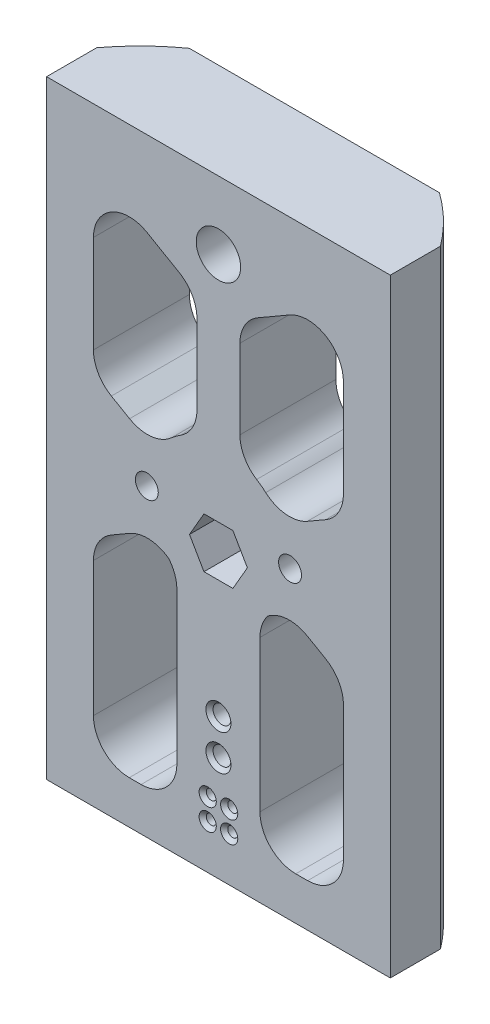
SolidWorks part; units mm, degrees
ref_plane "Front Plane" through (0, 0, 0) normal (0, 0, 1) x (1, 0, 0)
ref_plane "Top Plane" through (0, 0, 0) normal (0, 1, 0) x (1, 0, 0)
ref_plane "Right Plane" through (0, 0, 0) normal (1, 0, 0) x (0, 0, -1)
sketch "Sketch1" plane through (0, 0, 0) normal (0, 0, 1) x (1, 0, 0)
  line L0 (-2.275, -128.15) -> (-2.275, -128.6)
  line L1 (2.275, -128.15) -> (2.275, -128.6)
  line L2 (-2.275, -133.15) -> (-2.275, -134.025)
  line L3 (2.275, -133.15) -> (2.275, -134.025)
  line L11 (-2.275, -128.15) -> (2.275, -128.15)
  line L12 (2.275, -128.15) -> (2.275, -123.6)
  line L13 (2.275, -123.6) -> (-2.275, -123.6)
  line L14 (-2.275, -123.6) -> (-2.275, -128.15)
  line L15 (-2.275, -128.15) -> (2.275, -128.15)
  line L16 (2.275, -128.15) -> (2.275, -123.6)
  line L17 (2.275, -123.6) -> (-2.275, -123.6)
  line L18 (-2.275, -123.6) -> (-2.275, -128.15)
  line L24 (-2.275, -133.15) -> (2.275, -133.15)
  line L25 (2.275, -133.15) -> (2.275, -128.6)
  line L26 (2.275, -128.6) -> (-2.275, -128.6)
  line L27 (-2.275, -128.6) -> (-2.275, -133.15)
  line L28 (-2.275, -133.15) -> (2.275, -133.15)
  line L29 (2.275, -133.15) -> (2.275, -128.6)
  line L30 (2.275, -128.6) -> (-2.275, -128.6)
  line L31 (-2.275, -128.6) -> (-2.275, -133.15)
  line L37 (0, -123.6) -> (0, -142.4) construction
  line L39 (7, -120.5) -> (-7, -120.5)
  line L40 (7, -120.5) -> (7, -145.5)
  line L41 (7, -145.5) -> (-7, -145.5)
  line L42 (-7, -120.5) -> (-7, -145.5)
  line L43 (7, -120.5) -> (-7, -145.5) construction
  line L44 (7, -145.5) -> (-7, -120.5) construction
  line L45 (-1, -142.4) -> (1, -142.4)
  line L46 (1, -142.4) -> (1, -141.625)
  line L47 (1, -141.625) -> (3.8, -141.625)
  line L48 (3.8, -141.625) -> (3.8, -134.025)
  line L49 (3.8, -134.025) -> (-3.8, -134.025)
  line L50 (-3.8, -134.025) -> (-3.8, -141.625)
  line L51 (-3.8, -141.625) -> (-1, -141.625)
  line L52 (-1, -141.625) -> (-1, -142.4)
  line L53 (-1, -142.4) -> (1, -142.4)
  line L54 (1, -142.4) -> (1, -141.625)
  line L55 (1, -141.625) -> (3.8, -141.625)
  line L56 (3.8, -141.625) -> (3.8, -134.025)
  line L57 (3.8, -134.025) -> (-3.8, -134.025)
  line L58 (-3.8, -134.025) -> (-3.8, -141.625)
  line L59 (-3.8, -141.625) -> (-1, -141.625)
  line L60 (-1, -141.625) -> (-1, -142.4)
  circle A0 centre (0, -125.875) radius 1.275
  circle A1 centre (0, -130.875) radius 1.275
  circle A2 centre (-1.5, -139.325) radius 0.65
  circle A3 centre (-1.5, -136.325) radius 0.65
  circle A4 centre (1.5, -136.325) radius 0.65
  circle A5 centre (1.5, -139.325) radius 0.65
  point P25 (0, -133)
  dimension "D4" = 2.55
  dimension "D5" = 1.3
  dimension "D6" = 25
  dimension "D7" = 14
  dimension "D1" = 0.2
  dimension "D2" = 0.2
  dimension "D3" = 0.2
extrude "Boss-Extrude1" add sketch "Sketch1" against normal blind 6.4 contours L39 L42 L41 L40 L60 L59 L58 L57 L31 L18 L17 L16 L29 L56 L55 L54 L53 region at (6.7135, -133, 0)
sketch "Sketch3" plane through (0, 0, 0) normal (0, 0, 1) x (1, 0, 0)
  line L4 (7, -120.5) -> (-7, -120.5)
  line L5 (-7, -120.5) -> (-7, -145.5)
  line L6 (-7, -145.5) -> (7, -145.5)
  line L7 (7, -145.5) -> (7, -120.5)
  line L8 (7, -120.5) -> (-7, -120.5)
  line L9 (-7, -120.5) -> (-7, -145.5)
  line L10 (-7, -145.5) -> (7, -145.5)
  line L11 (7, -145.5) -> (7, -120.5)
  circle A0 centre (-1.5, -139.325) radius 0.7
  circle A1 centre (-1.5, -136.325) radius 0.7
  circle A2 centre (1.5, -136.325) radius 0.7
  circle A3 centre (1.5, -139.325) radius 0.7
  circle A4 centre (0, -130.875) radius 1.25
  circle A5 centre (0, -125.875) radius 1.25
  dimension "D2" = 2.5
  dimension "D3" = 1.4
  dimension "D1" = 0
extrude "Boss-Extrude3" add sketch "Sketch3" along normal blind 7
chamfer "Chamfer1" distance 0.5 angle 45 6 edges at (2.2, -139.325, 7) (-0.8, -139.325, 7) (-0.8, -136.325, 7) (2.2, -136.325, 7) (1.25, -130.875, 7) (1.25, -125.875, 7)
sketch "Sketch4" plane through (0, -145.5, 0) normal (0, -1, 0) x (1, 0, 0)
  line L0 (-7, -6.4) -> (-17.4539, -6.4)
  line L1 (-7, 7) -> (-27.9106, 7)
  line L2 (7, -6.4) -> (17.4539, -6.4)
  line L3 (7, 7) -> (27.9106, 7)
  line L4 (-24, 0) -> (-24, 7)
  line L5 (24, 0) -> (24, 7)
  circle A4 centre (0, 18) radius 30
  arc A5 (-24, 0) -> (24, 0) centre (0, 18) ccw construction
  line M2 (7, -6.4) -> (7, 7)
  line M4 (-7, 7) -> (-7, -6.4)
extrude "Boss-Extrude4" add sketch "Sketch4" against normal up to surface (25 mm away) contours L1 A4 L0 M4 | L2 A4 L3 M2 region at (-14.9215, -145.5, 0.7207) region at (14.9215, -145.5, 0.7207) up to face at (0, -120.5, 0.3)
sketch "Sketch5" plane through (0, -120.5, 0) normal (0, 1, 0) x (1, 0, 0)
  line L2 (17.4539, 6.4) -> (-17.4539, 6.4)
  line L3 (-24, -7) -> (24, -7)
  line L4 (17.4539, 6.4) -> (-17.4539, 6.4)
  line L5 (-24, -7) -> (24, -7)
  line L8 (-24, 0) -> (-24, -7)
  line L9 (-24, 0) -> (-24, -7)
  line L10 (24, -7) -> (24, 0)
  line L11 (24, -7) -> (24, 0)
  arc A2 (-17.4539, 6.4) -> (-24, 0) centre (0, -18) ccw
  arc A3 (24, 0) -> (17.4539, 6.4) centre (0, -18) ccw
  arc A4 (-17.4539, 6.4) -> (-24, 0) centre (0, -18) ccw
  arc A5 (24, 0) -> (17.4539, 6.4) centre (0, -18) ccw
  dimension "D1" = 0
extrude "Boss-Extrude5" add sketch "Sketch5" along normal blind 60
sketch "Sketch6" plane through (0, 0, 7) normal (0, 0, 1) x (1, 0, 0)
  line L0 (0, -60.5) -> (0, -145.5) construction
  line L1 (-24, -60.5) -> (24, -60.5) construction
  line L2 (-24, -145.5) -> (24, -145.5) construction
  circle A0 centre (0, -105.875) radius 2.25
  circle A3 centre (0, -105.875) radius 2.25 construction
  dimension "D2" = 4.5
extrude "Cut-Extrude1" cut sketch "Sketch6" against normal up to next
sketch "Sketch7" plane through (0, 0, 7) normal (0, 0, 1) x (1, 0, 0)
  line L1 (4.0415, -105.875) -> (2.0207, -102.375)
  line L2 (2.0207, -102.375) -> (-2.0207, -102.375)
  line L3 (-2.0207, -102.375) -> (-4.0415, -105.875)
  line L4 (-4.0415, -105.875) -> (-2.0207, -109.375)
  line L5 (-2.0207, -109.375) -> (2.0207, -109.375)
  line L6 (2.0207, -109.375) -> (4.0415, -105.875)
  circle A0 centre (0, -105.875) radius 3.5 construction
  dimension "D1" = 7
extrude "Cut-Extrude2" cut sketch "Sketch7" against normal offset from surface (7.4 mm away) 6 up to face at (2.25, -105.875, -6.4)
sketch "Sketch9" plane through (0, 0, -6.4) normal (0, 0, -1) x (-1, 0, 0)
  line L0 (-24, -103) -> (24, -103) construction
  line L1 (-24, -60.5) -> (-24, -145.5) construction
  line L2 (24, -60.5) -> (24, -145.5) construction
  line L3 (0, -60.5) -> (0, -145.5) construction
  line L4 (-17.4539, -60.5) -> (17.4539, -60.5) construction
  line L5 (-17.4539, -145.5) -> (17.4539, -145.5) construction
  circle A0 centre (-10, -103) radius 1.6
  circle A1 centre (10, -103) radius 1.6
  dimension "D1" = 3.2
  dimension "D2" = 20
extrude "Cut-Extrude4" cut sketch "Sketch9" against normal up to next
sketch "Sketch10" plane through (0, 0, -6.4) normal (0, 0, -1) x (-1, 0, 0)
  line L0 (0, -60.5) -> (0, -145.5) construction
  line L1 (-10, -106.2332) -> (-7.2, -104.6166)
  line L2 (-7.2, -104.6166) -> (-7.2, -101.3834)
  line L3 (-7.2, -101.3834) -> (-10, -99.7668)
  line L4 (-10, -99.7668) -> (-12.8, -101.3834)
  line L5 (-12.8, -101.3834) -> (-12.8, -104.6166)
  line L6 (-12.8, -104.6166) -> (-10, -106.2332)
  line L7 (-17.4539, -60.5) -> (17.4539, -60.5) construction
  line L8 (-17.4539, -145.5) -> (17.4539, -145.5) construction
  line L9 (12.8, -104.6166) -> (10, -106.2332)
  line L10 (12.8, -101.3834) -> (12.8, -104.6166)
  line L11 (10, -99.7668) -> (12.8, -101.3834)
  line L12 (7.2, -101.3834) -> (10, -99.7668)
  line L13 (7.2, -104.6166) -> (7.2, -101.3834)
  line L14 (10, -106.2332) -> (7.2, -104.6166)
  circle A0 centre (-10, -103) radius 2.8 construction
  dimension "D1" = 5.6
extrude "Cut-Extrude5" cut sketch "Sketch10" against normal offset from surface (7.4 mm away) 6 up to face at (11.6, -103, 7)
sketch "Sketch11" plane through (0, 0, 7) normal (0, 0, 1) x (1, 0, 0)
  line L0 (0, -60.5) -> (0, -145.5) construction
  line L1 (-24, -60.5) -> (24, -60.5) construction
  line L2 (-24, -145.5) -> (24, -145.5) construction
  circle A0 centre (0, -70) radius 3.1
  circle A1 centre (0, -70) radius 9.5
  dimension "D1" = 19
  dimension "D2" = 6.2
extrude "Cut-Extrude6" cut sketch "Sketch11" against normal up to next contours A0
sketch "Sketch12" plane through (0, 0, -6.4) normal (0, 0, -1) x (-1, 0, 0)
  line L1 (0, -64.2265) -> (-5, -67.1132)
  line L2 (-5, -67.1132) -> (-5, -72.8868)
  line L3 (-5, -72.8868) -> (0, -75.7735)
  line L4 (0, -75.7735) -> (5, -72.8868)
  line L5 (5, -72.8868) -> (5, -67.1132)
  line L6 (5, -67.1132) -> (0, -64.2265)
  circle A0 centre (0, -70) radius 5 construction
  dimension "D1" = 10
extrude "Cut-Extrude7" cut sketch "Sketch12" against normal blind 6
sketch "Sketch13" plane through (0, 0, -6.4) normal (0, 0, -1) x (-1, 0, 0)
  line L0 (-7, -74.0415) -> (-17.4539, -68.0059)
  line L1 (-3, -78.0829) -> (-3, -76.3509)
  line L2 (-3, -101.4989) -> (-17.4539, -93.1539)
  line L3 (3, -78.0829) -> (3, -76.3509)
  line L4 (7, -74.0415) -> (17.4539, -68.0059)
  line L5 (3, -101.4989) -> (17.4539, -93.1539)
  line L6 (-3, -104.5011) -> (-17.4539, -112.8461)
  line L7 (3, -104.5011) -> (17.4539, -112.8461)
  line L8 (17.4539, -145.5) -> (17.4539, -60.5)
  line L9 (17.4539, -60.5) -> (-17.4539, -60.5)
  line L10 (-17.4539, -60.5) -> (-17.4539, -145.5)
  line L11 (-17.4539, -145.5) -> (17.4539, -145.5)
  line L12 (17.4539, -145.5) -> (17.4539, -60.5)
  line L13 (17.4539, -60.5) -> (-17.4539, -60.5)
  line L14 (-17.4539, -60.5) -> (-17.4539, -145.5)
  line L15 (-17.4539, -145.5) -> (17.4539, -145.5)
  line L16 (-17.4539, -139.5) -> (17.4539, -139.5)
  line L17 (-5.2, -103) -> (5.2, -103) construction
  line L18 (-5.8, -132.025) -> (-5.8, -111.1462)
  line L19 (5.8, -132.025) -> (5.8, -111.1462)
  line L32 (0, -78.0829) -> (0, -121.6) construction
  line L33 (-3, -78.0829) -> (-3, -121.6)
  line L34 (3, -78.0829) -> (3, -121.6)
  line L37 (3, -144.4) -> (3, -143.625)
  line L38 (3, -143.625) -> (5.8, -143.625)
  line L39 (5.8, -143.625) -> (5.8, -132.025)
  line L40 (5.8, -132.025) -> (4.275, -132.025)
  line L41 (4.275, -132.025) -> (4.275, -121.6)
  line L42 (4.275, -121.6) -> (-4.275, -121.6)
  line L43 (-4.275, -121.6) -> (-4.275, -132.025)
  line L44 (-4.275, -132.025) -> (-5.8, -132.025)
  line L45 (-5.8, -132.025) -> (-5.8, -143.625)
  line L46 (-5.8, -143.625) -> (-3, -143.625)
  line L47 (-3, -143.625) -> (-3, -144.4)
  line L48 (-3, -144.4) -> (3, -144.4)
  line L49 (3, -144.4) -> (3, -143.625)
  line L50 (3, -143.625) -> (5.8, -143.625)
  line L51 (5.8, -143.625) -> (5.8, -132.025)
  line L52 (5.8, -132.025) -> (4.275, -132.025)
  line L53 (4.275, -132.025) -> (4.275, -121.6)
  line L54 (4.275, -121.6) -> (-4.275, -121.6)
  line L55 (-4.275, -121.6) -> (-4.275, -132.025)
  line L56 (-4.275, -132.025) -> (-5.8, -132.025)
  line L57 (-5.8, -132.025) -> (-5.8, -143.625)
  line L58 (-5.8, -143.625) -> (-3, -143.625)
  line L59 (-3, -143.625) -> (-3, -144.4)
  line L60 (-3, -144.4) -> (3, -144.4)
  line L62 (0, -61.9171) -> (-7, -65.9585)
  line L63 (7, -65.9585) -> (0, -61.9171)
  line L64 (7, -74.0415) -> (7, -65.9585)
  line L65 (0, -78.0829) -> (7, -74.0415)
  line L66 (-7, -74.0415) -> (0, -78.0829)
  line L67 (-7, -65.9585) -> (-7, -74.0415)
  line L68 (0, -61.9171) -> (-7, -65.9585)
  line L69 (7, -65.9585) -> (0, -61.9171)
  line L70 (7, -74.0415) -> (7, -65.9585)
  line L71 (0, -78.0829) -> (7, -74.0415)
  line L72 (-7, -74.0415) -> (0, -78.0829)
  line L73 (-7, -65.9585) -> (-7, -74.0415)
  line L83 (-14.8, -105.7713) -> (-10, -108.5426)
  line L84 (-10, -108.5426) -> (-5.2, -105.7713)
  line L85 (-5.2, -105.7713) -> (-5.2, -100.2287)
  line L86 (-5.2, -100.2287) -> (-10, -97.4574)
  line L87 (-10, -97.4574) -> (-14.8, -100.2287)
  line L88 (-14.8, -100.2287) -> (-14.8, -105.7713)
  line L89 (-14.8, -105.7713) -> (-10, -108.5426)
  line L90 (-10, -108.5426) -> (-5.2, -105.7713)
  line L91 (-5.2, -105.7713) -> (-5.2, -100.2287)
  line L92 (-5.2, -100.2287) -> (-10, -97.4574)
  line L93 (-10, -97.4574) -> (-14.8, -100.2287)
  line L94 (-14.8, -100.2287) -> (-14.8, -105.7713)
  line L95 (-10.8, -103.4619) -> (-10, -103.9238)
  line L96 (-10, -103.9238) -> (-9.2, -103.4619)
  line L97 (-9.2, -103.4619) -> (-9.2, -102.5381)
  line L98 (-9.2, -102.5381) -> (-10, -102.0762)
  line L99 (-10, -102.0762) -> (-10.8, -102.5381)
  line L100 (-10.8, -102.5381) -> (-10.8, -103.4619)
  line L101 (-10.8, -103.4619) -> (-10, -103.9238)
  line L102 (-10, -103.9238) -> (-9.2, -103.4619)
  line L103 (-9.2, -103.4619) -> (-9.2, -102.5381)
  line L104 (-9.2, -102.5381) -> (-10, -102.0762)
  line L105 (-10, -102.0762) -> (-10.8, -102.5381)
  line L106 (-10.8, -102.5381) -> (-10.8, -103.4619)
  line L114 (10, -97.4574) -> (5.2, -100.2287)
  line L115 (14.8, -100.2287) -> (10, -97.4574)
  line L116 (14.8, -105.7713) -> (14.8, -100.2287)
  line L117 (10, -108.5426) -> (14.8, -105.7713)
  line L118 (5.2, -105.7713) -> (10, -108.5426)
  line L119 (5.2, -100.2287) -> (5.2, -105.7713)
  line L120 (10, -97.4574) -> (5.2, -100.2287)
  line L121 (14.8, -100.2287) -> (10, -97.4574)
  line L122 (14.8, -105.7713) -> (14.8, -100.2287)
  line L123 (10, -108.5426) -> (14.8, -105.7713)
  line L124 (5.2, -105.7713) -> (10, -108.5426)
  line L125 (5.2, -100.2287) -> (5.2, -105.7713)
  line L126 (10, -102.0762) -> (9.2, -102.5381)
  line L127 (10.8, -102.5381) -> (10, -102.0762)
  line L128 (10.8, -103.4619) -> (10.8, -102.5381)
  line L129 (10, -103.9238) -> (10.8, -103.4619)
  line L130 (9.2, -103.4619) -> (10, -103.9238)
  line L131 (9.2, -102.5381) -> (9.2, -103.4619)
  line L132 (10, -102.0762) -> (9.2, -102.5381)
  line L133 (10.8, -102.5381) -> (10, -102.0762)
  line L134 (10.8, -103.4619) -> (10.8, -102.5381)
  line L135 (10, -103.9238) -> (10.8, -103.4619)
  line L136 (9.2, -103.4619) -> (10, -103.9238)
  line L137 (9.2, -102.5381) -> (9.2, -103.4619)
  circle A0 centre (0, -103) radius 10
  circle M74 centre (0, -105.875) radius 2.25
  line M87 (17.4539, -145.5) -> (17.4539, -60.5)
  line M89 (-17.4539, -60.5) -> (-17.4539, -145.5)
  dimension "D10" = 6
  dimension "D1" = 0
  dimension "D2" = 2
  dimension "D3" = 2
  dimension "D4" = 3
  dimension "D5" = 3
  dimension "D6" = 2
  dimension "D7" = 2
  dimension "D8" = 2
  dimension "D9" = 2
extrude "Cut-Extrude8" cut sketch "Sketch13" against normal up to next contours L72 L0 L2 L33 L1 M89 | L71 L3 L34 L5 L4 M87 | L57 L56 L55 L54 L33 L6 L16 M74 M89 | L54 L53 L52 L51 L16 L12 L7 L34 M74 region at (10.6361, -83.7462, -6.4) region at (11.5188, -124.8103, -6.4) region at (-10.6361, -83.7462, -6.4) region at (-11.5188, -124.8103, -6.4)
fillet "Fillet1" radius 5 20 edges at (5.8, -111.1462, 0.3) (8.7585, -107.8258, 0.3) (17.4539, -112.8461, 0.3) (17.4539, -139.5, 0.3) (5.8, -139.5, 0.3) (-17.4539, -139.5, 0.3) (-5.8, -139.5, 0.3) (-5.8, -111.1462, 0.3) (-8.7585, -107.8258, 0.3) (-17.4539, -112.8461, 0.3) (-17.4539, -68.0059, 0.3) (-17.4539, -93.1539, 0.3) (-8.7585, -98.1742, 0.3) (-3, -93.4606, 0.3) (-3, -76.3509, 0.3) (3, -76.3509, 0.3) (3, -93.4606, 0.3) (8.7585, -98.1742, 0.3) (17.4539, -93.1539, 0.3) (17.4539, -68.0059, 0.3)
